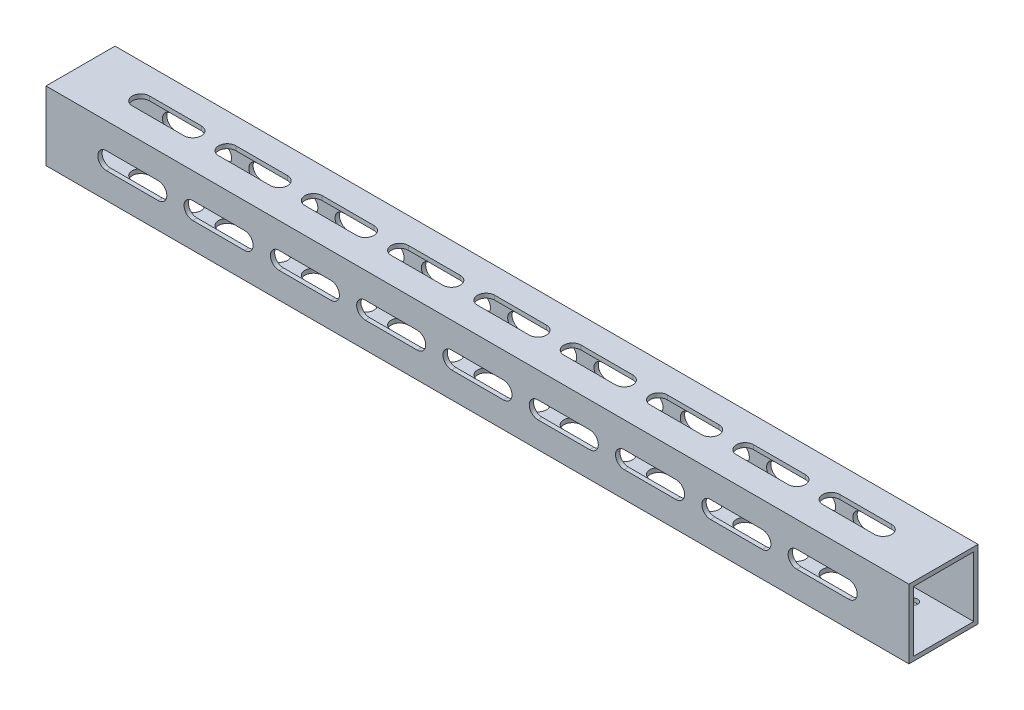
SolidWorks part; units mm, degrees
material "6061-T6 (SS)"
ref_plane "Front" through (0, 0, 0) normal (0, 0, 1) x (1, 0, 0)
ref_plane "Top" through (0, 0, 0) normal (0, 1, 0) x (1, 0, 0)
ref_plane "Right" through (0, 0, 0) normal (1, 0, 0) x (0, 0, -1)
sketch "Sketch1" plane through (0, 0, 0) normal (1, 0, 0) x (0, 0, -1)
  line L1 (-12.7, -12.7) -> (12.7, -12.7)
  line L2 (-12.7, -12.7) -> (-12.7, 12.7)
  line L3 (-12.7, 12.7) -> (12.7, 12.7)
  line L4 (12.7, -12.7) -> (12.7, 12.7)
  line L5 (-12.7, -12.7) -> (12.7, 12.7) construction
  line L6 (-12.7, 12.7) -> (12.7, -12.7) construction
  point P0 (0, 0)
  dimension "D1" = 25.4
extrude "Extrude-Thin1" add sketch "Sketch1" along normal up to surface (317.5 mm away) thin thin type one direction reverse wall 1.5875
sketch "Sketch4" plane through (0, -12.7, 0) normal (0, -1, 0) x (1, 0, 0)
  line L0 (0, 12.7) -> (0, -12.7) construction
  line L2 (17.4625, -6.35) -> (0, 0) construction
  line L3 (0, 0) -> (17.4625, 6.35) construction
  line L4 (158.75, -12.7) -> (158.75, 38.5816) construction
  line L5 (317.5, -12.7) -> (0, -12.7) construction
  point P0 (17.4625, -6.35)
  point P2 (26.9875, 6.35)
  point P7 (26.9875, -6.35)
  point P10 (17.4625, 6.35)
  point P22 (71.4375, -6.35)
  point P24 (61.9125, -6.35)
  point P26 (61.9125, 6.35)
  point P28 (71.4375, 6.35)
  point P37 (246.0625, 6.35)
  point P38 (255.5875, 6.35)
  point P39 (255.5875, -6.35)
  point P40 (246.0625, -6.35)
  point P41 (300.0375, 6.35)
  point P42 (290.5125, -6.35)
  point P43 (290.5125, 6.35)
  point P44 (300.0375, -6.35)
  dimension "D1" = 17.4625
  dimension "D2" = 9.525
  dimension "D3" = 12.7
  dimension "D4" = 44.45
  dimension "D5" = 9.525
hole_wizard "#30 (0.13) Diameter Hole1" positions "Sketch4" profile "Sketch3" hole size "#30" standard "ANSI Inch" end condition up to next
sketch "Sketch3" plane through (17.4625, -12.7, -6.35) normal (1, 0, 0) x (0, 0, -1)
  line L0 (0, 0) -> (0, 1.5875)
  line L1 (0, 1.5875) -> (1.651, 1.5875)
  line L2 (1.651, 1.5875) -> (1.651, 0)
  line L5 (1.651, 0) -> (0, 0)
  line L11 (0, -6.35) -> (0, 107.95) construction
  dimension "Thru Hole Dia." = 3.302
  dimension "Thru Hole Depth" = 1.5875
sketch "Sketch5" plane through (0, 12.7, 0) normal (0, 1, 0) x (1, 0, 0)
  line L0 (22.225, 0) -> (41.275, 0) construction
  line L1 (22.225, 3.175) -> (41.275, 3.175)
  line L2 (22.225, -3.175) -> (41.275, -3.175)
  line L3 (0, 12.7) -> (0, -12.7) construction
  line L4 (53.975, 0) -> (73.025, 0) construction
  line L5 (53.975, 3.175) -> (73.025, 3.175)
  line L6 (53.975, -3.175) -> (73.025, -3.175)
  line L7 (85.725, 0) -> (104.775, 0) construction
  line L8 (85.725, 3.175) -> (104.775, 3.175)
  line L9 (85.725, -3.175) -> (104.775, -3.175)
  line L10 (117.475, 0) -> (136.525, 0) construction
  line L11 (117.475, 3.175) -> (136.525, 3.175)
  line L12 (117.475, -3.175) -> (136.525, -3.175)
  line L13 (149.225, 0) -> (168.275, 0) construction
  line L14 (149.225, 3.175) -> (168.275, 3.175)
  line L15 (149.225, -3.175) -> (168.275, -3.175)
  line L16 (180.975, 0) -> (200.025, 0) construction
  line L17 (180.975, 3.175) -> (200.025, 3.175)
  line L18 (180.975, -3.175) -> (200.025, -3.175)
  line L19 (212.725, 0) -> (231.775, 0) construction
  line L20 (212.725, 3.175) -> (231.775, 3.175)
  line L21 (212.725, -3.175) -> (231.775, -3.175)
  line L22 (244.475, 0) -> (263.525, 0) construction
  line L23 (244.475, 3.175) -> (263.525, 3.175)
  line L24 (244.475, -3.175) -> (263.525, -3.175)
  line L25 (276.225, 0) -> (295.275, 0) construction
  line L26 (276.225, 3.175) -> (295.275, 3.175)
  line L27 (276.225, -3.175) -> (295.275, -3.175)
  arc A0 (22.225, 3.175) -> (22.225, -3.175) centre (22.225, 0) ccw
  arc A1 (41.275, -3.175) -> (41.275, 3.175) centre (41.275, 0) ccw
  arc A2 (53.975, 3.175) -> (53.975, -3.175) centre (53.975, 0) ccw
  arc A3 (73.025, -3.175) -> (73.025, 3.175) centre (73.025, 0) ccw
  arc A4 (85.725, 3.175) -> (85.725, -3.175) centre (85.725, 0) ccw
  arc A5 (104.775, -3.175) -> (104.775, 3.175) centre (104.775, 0) ccw
  arc A6 (117.475, 3.175) -> (117.475, -3.175) centre (117.475, 0) ccw
  arc A7 (136.525, -3.175) -> (136.525, 3.175) centre (136.525, 0) ccw
  arc A8 (149.225, 3.175) -> (149.225, -3.175) centre (149.225, 0) ccw
  arc A9 (168.275, -3.175) -> (168.275, 3.175) centre (168.275, 0) ccw
  arc A10 (180.975, 3.175) -> (180.975, -3.175) centre (180.975, 0) ccw
  arc A11 (200.025, -3.175) -> (200.025, 3.175) centre (200.025, 0) ccw
  arc A12 (212.725, 3.175) -> (212.725, -3.175) centre (212.725, 0) ccw
  arc A13 (231.775, -3.175) -> (231.775, 3.175) centre (231.775, 0) ccw
  arc A14 (244.475, 3.175) -> (244.475, -3.175) centre (244.475, 0) ccw
  arc A15 (263.525, -3.175) -> (263.525, 3.175) centre (263.525, 0) ccw
  arc A16 (276.225, 3.175) -> (276.225, -3.175) centre (276.225, 0) ccw
  arc A17 (295.275, -3.175) -> (295.275, 3.175) centre (295.275, 0) ccw
  point P2 (31.75, 0)
  point P13 (63.5, 0)
  point P20 (95.25, 0)
  point P27 (127, 0)
  point P34 (158.75, 0)
  point P41 (190.5, 0)
  point P48 (222.25, 0)
  point P55 (254, 0)
  point P62 (285.75, 0)
  dimension "D3" = 22.225
  dimension "D5" = 12.7
  dimension "D1" = 6.35
  dimension "D2" = 19.05
  dimension "D4" = 9
extrude "Cut-Extrude1" cut sketch "Sketch5" against normal through all
sketch "Sketch6" plane through (0, 0, 12.7) normal (0, 0, 1) x (1, 0, 0)
  line L0 (22.225, 0) -> (41.275, 0) construction
  line L1 (22.225, 3.175) -> (41.275, 3.175)
  line L2 (22.225, -3.175) -> (41.275, -3.175)
  line L3 (0, 12.7) -> (0, -12.7) construction
  line L4 (53.975, 0) -> (73.025, 0) construction
  line L5 (53.975, 3.175) -> (73.025, 3.175)
  line L6 (53.975, -3.175) -> (73.025, -3.175)
  line L7 (85.725, 0) -> (104.775, 0) construction
  line L8 (85.725, 3.175) -> (104.775, 3.175)
  line L9 (85.725, -3.175) -> (104.775, -3.175)
  line L10 (117.475, 0) -> (136.525, 0) construction
  line L11 (117.475, 3.175) -> (136.525, 3.175)
  line L12 (117.475, -3.175) -> (136.525, -3.175)
  line L13 (149.225, 0) -> (168.275, 0) construction
  line L14 (149.225, 3.175) -> (168.275, 3.175)
  line L15 (149.225, -3.175) -> (168.275, -3.175)
  line L16 (180.975, 0) -> (200.025, 0) construction
  line L17 (180.975, 3.175) -> (200.025, 3.175)
  line L18 (180.975, -3.175) -> (200.025, -3.175)
  line L19 (212.725, 0) -> (231.775, 0) construction
  line L20 (212.725, 3.175) -> (231.775, 3.175)
  line L21 (212.725, -3.175) -> (231.775, -3.175)
  line L22 (244.475, 0) -> (263.525, 0) construction
  line L23 (244.475, 3.175) -> (263.525, 3.175)
  line L24 (244.475, -3.175) -> (263.525, -3.175)
  line L25 (276.225, 0) -> (295.275, 0) construction
  line L26 (276.225, 3.175) -> (295.275, 3.175)
  line L27 (276.225, -3.175) -> (295.275, -3.175)
  arc A0 (22.225, 3.175) -> (22.225, -3.175) centre (22.225, 0) ccw
  arc A1 (41.275, -3.175) -> (41.275, 3.175) centre (41.275, 0) ccw
  arc A2 (53.975, 3.175) -> (53.975, -3.175) centre (53.975, 0) ccw
  arc A3 (73.025, -3.175) -> (73.025, 3.175) centre (73.025, 0) ccw
  arc A4 (85.725, 3.175) -> (85.725, -3.175) centre (85.725, 0) ccw
  arc A5 (104.775, -3.175) -> (104.775, 3.175) centre (104.775, 0) ccw
  arc A6 (117.475, 3.175) -> (117.475, -3.175) centre (117.475, 0) ccw
  arc A7 (136.525, -3.175) -> (136.525, 3.175) centre (136.525, 0) ccw
  arc A8 (149.225, 3.175) -> (149.225, -3.175) centre (149.225, 0) ccw
  arc A9 (168.275, -3.175) -> (168.275, 3.175) centre (168.275, 0) ccw
  arc A10 (180.975, 3.175) -> (180.975, -3.175) centre (180.975, 0) ccw
  arc A11 (200.025, -3.175) -> (200.025, 3.175) centre (200.025, 0) ccw
  arc A12 (212.725, 3.175) -> (212.725, -3.175) centre (212.725, 0) ccw
  arc A13 (231.775, -3.175) -> (231.775, 3.175) centre (231.775, 0) ccw
  arc A14 (244.475, 3.175) -> (244.475, -3.175) centre (244.475, 0) ccw
  arc A15 (263.525, -3.175) -> (263.525, 3.175) centre (263.525, 0) ccw
  arc A16 (276.225, 3.175) -> (276.225, -3.175) centre (276.225, 0) ccw
  arc A17 (295.275, -3.175) -> (295.275, 3.175) centre (295.275, 0) ccw
  point P3 (31.75, 0)
  point P13 (63.5, 0)
  point P20 (95.25, 0)
  point P27 (127, 0)
  point P34 (158.75, 0)
  point P41 (190.5, 0)
  point P48 (222.25, 0)
  point P55 (254, 0)
  point P62 (285.75, 0)
  dimension "D3" = 22.225
  dimension "D5" = 12.7
  dimension "D1" = 6.35
  dimension "D2" = 19.05
  dimension "D4" = 9
extrude "Cut-Extrude2" cut sketch "Sketch6" against normal through all
